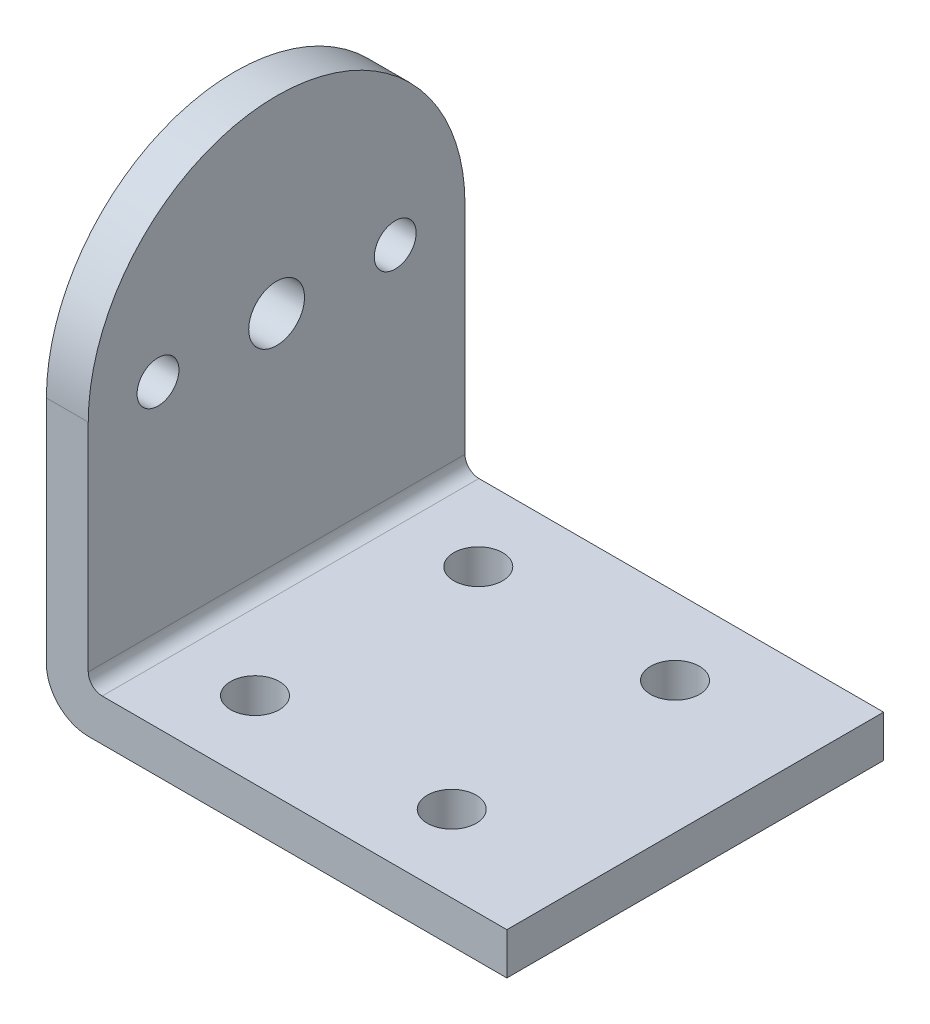
SolidWorks part; units mm, degrees
ref_plane "Přední rovina" through (0, 0, 0) normal (0, 0, 1) x (1, 0, 0)
ref_plane "Horní rovina" through (0, 0, 0) normal (0, 1, 0) x (1, 0, 0)
ref_plane "Pravá rovina" through (0, 0, 0) normal (1, 0, 0) x (0, 0, -1)
sketch "Skica1" plane through (0, 0, 0) normal (0, 0, 1) x (1, 0, 0)
  line L0 (0, 0) -> (0, 33)
  line L1 (0, 33) -> (3, 33)
  line L2 (3, 33) -> (3, 3)
  line L3 (3, 3) -> (33, 3)
  line L4 (33, 3) -> (33, 0)
  line L5 (33, 0) -> (0, 0)
  dimension "D1" = 33
  dimension "D2" = 33
  dimension "D3" = 3
  dimension "D4" = 3
extrude "Přidat vysunutím1" add sketch "Skica1" along normal blind 27
fillet "Zaoblit1" radius 1 1 edges at (3, 3, 13.5)
sketch "Skica2" plane through (0, 0, 0) normal (0, -1, 0) x (1, 0, 0)
  line L0 (0, 13.5) -> (33, 13.5) construction
  line L1 (0, 27) -> (0, 0) construction
  line L2 (33, 27) -> (33, 0) construction
  line L3 (16.5, 27) -> (16.5, 0) construction
  line L4 (0, 27) -> (33, 27) construction
  line L5 (0, 0) -> (33, 0) construction
  line L6 (9.45, 21.5) -> (23.55, 21.5) construction
  circle A0 centre (9.45, 21.5) radius 1.75
  circle A1 centre (23.55, 21.5) radius 1.75
  circle A2 centre (23.55, 5.5) radius 1.75
  circle A3 centre (9.45, 5.5) radius 1.75
  dimension "D1" = 3.5
  dimension "D2" = 3.5
  dimension "D3" = 14.1
  dimension "D4" = 16
  dimension "D5" = 9.45
extrude "Odebrat vysunutím1" cut sketch "Skica2" against normal blind 3
fillet "Zaoblit2" radius 3 1 edges at (0, 0, 13.5)
sketch "Skica3" plane through (0, 0, 0) normal (-1, 0, 0) x (0, 0, 1)
  line L0 (13.5, 33) -> (13.5, 3) construction
  line L1 (27, 33) -> (0, 33) construction
  line L2 (0, 3) -> (27, 3) construction
  line L3 (0, 19.5) -> (27, 19.5) construction
  line L4 (0, 19.5) -> (0, 33)
  line L5 (0, 33) -> (27, 33)
  line L6 (27, 33) -> (27, 19.5)
  arc A0 (27, 19.5) -> (0, 19.5) centre (13.5, 19.5) ccw
  circle A2 centre (5, 19.5) radius 1.5
  circle A3 centre (22, 19.5) radius 1.5
  circle A4 centre (13.5, 19.5) radius 2
  line M2 (0, 33) -> (0, 3)
  line M4 (27, 3) -> (27, 33)
  line M5 (27, 33) -> (0, 33)
  dimension "D1" = 27
  dimension "D2" = 4
  dimension "D4" = 3
  dimension "D3" = 17
extrude "Odebrat vysunutím2" cut sketch "Skica3" against normal blind 3 contours A0 M4 M5 | A0 L5 M2 region at (0, 29.9845, 23.9845) region at (0, 29.9845, 3.0155)
extrude "Odebrat vysunutím3" cut sketch "Skica3<3>" against normal blind 3 contours A2 | A3 region at (0, 19.5, 5) region at (0, 19.5, 22)
sketch "Skica3<3>" plane through (0, 0, 0) normal (-1, 0, 0) x (0, 0, 1) same geometry as "Skica3"
extrude "Odebrat vysunutím4" cut sketch "Skica3<4>" against normal blind 3 contours A4 region at (0, 19.5, 13.5)
sketch "Skica3<4>" plane through (0, 0, 0) normal (-1, 0, 0) x (0, 0, 1) same geometry as "Skica3"
